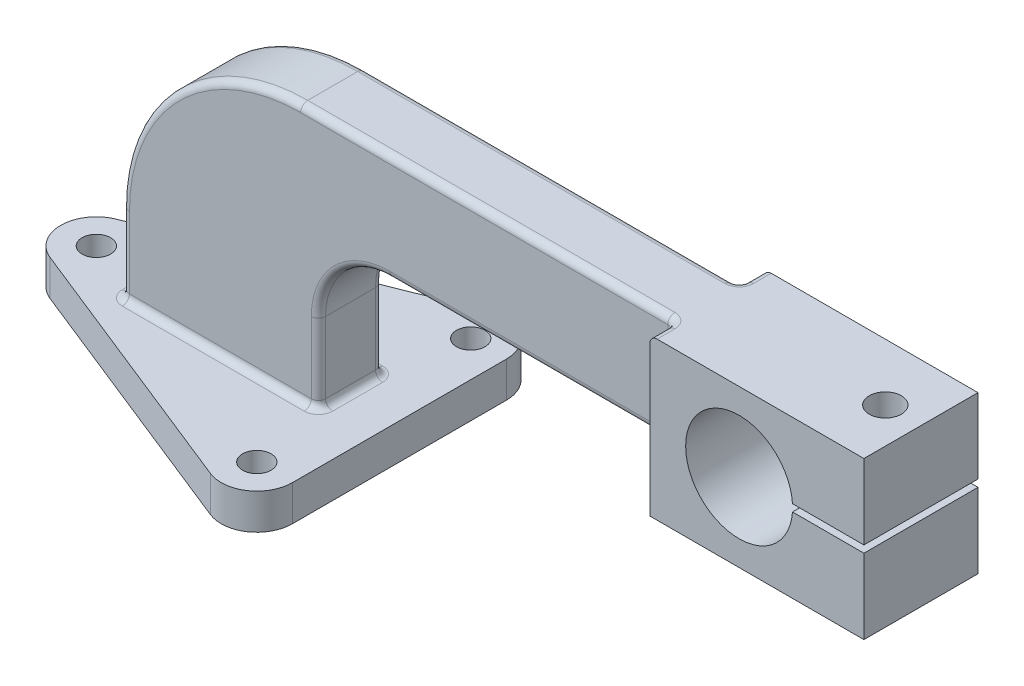
SolidWorks part; units mm, degrees
ref_plane "Front Plane" through (0, 0, 0) normal (0, 0, 1) x (1, 0, 0)
ref_plane "Top Plane" through (0, 0, 0) normal (0, 1, 0) x (1, 0, 0)
ref_plane "Right Plane" through (0, 0, 0) normal (1, 0, 0) x (0, 0, -1)
sketch "Sketch1" plane through (0, 0, 0) normal (0, 1, 0) x (1, 0, 0)
  line L0 (23.2119, 9.2848) -> (98.2119, 39.2848)
  line L1 (111.9258, 30) -> (111.9258, -30)
  line L2 (98.2119, -39.2848) -> (23.2119, -9.2848)
  line L3 (-21.5344, 0) -> (141.3067, 0) construction
  arc A0 (111.9258, -30) -> (98.2119, -39.2848) centre (101.9258, -30) cw
  arc A1 (23.2119, 9.2848) -> (23.2119, -9.2848) centre (26.9258, 0) ccw
  arc A2 (98.2119, 39.2848) -> (111.9258, 30) centre (101.9258, 30) cw
  circle A3 centre (26.9258, 0) radius 4
  circle A4 centre (101.9258, 30) radius 4
  circle A5 centre (101.9258, -30) radius 4
  point P13 (0, 0)
  dimension "D1" = 10
  dimension "D2" = 8
  dimension "D3" = 75
  dimension "D4" = 60
extrude "Boss-Extrude1" add sketch "Sketch1" along normal blind 10
sketch "Sketch2" plane through (0, 0, 0) normal (0, 0, 1) x (1, 0, 0)
  line L0 (43.2119, 10) -> (43.2119, 32)
  line L1 (23.2119, 10) -> (98.2119, 10) construction
  line L2 (98.2119, 10) -> (98.2119, 32)
  line L3 (93.2119, 82) -> (198.2119, 82)
  line L4 (223.2119, 60) -> (258.2119, 60) construction
  line L5 (198.2119, 82) -> (258.2119, 82)
  line L6 (258.2119, 82) -> (258.2119, 38)
  line L7 (258.2119, 38) -> (198.2119, 38)
  line L8 (198.2119, 38) -> (198.2119, 52)
  line L9 (198.2119, 52) -> (118.2119, 52)
  line L10 (98.2119, 10) -> (43.2119, 10)
  line L11 (198.2119, 82) -> (198.2119, 52)
  line L12 (198.2119, 52) -> (198.4483, 50.3894)
  line L14 (234.0634, 61) -> (282.3604, 61)
  line L15 (234.0634, 61) -> (234.0634, 59)
  line L16 (234.0634, 59) -> (282.3604, 59)
  line L17 (282.3604, 61) -> (282.3604, 59)
  line L18 (234.0634, 61) -> (282.3604, 59) construction
  line L19 (234.0634, 59) -> (282.3604, 61) construction
  arc A0 (43.2119, 32) -> (93.2119, 82) centre (93.2119, 32) cw
  arc A1 (98.2119, 32) -> (118.2119, 52) centre (118.2119, 32) cw
  circle A2 centre (223.2119, 60) radius 15
  dimension "D3" = 50
  dimension "D4" = 20
  dimension "D10" = 35
  dimension "D11" = 30
  dimension "D1" = 20
  dimension "D2" = 55
  dimension "D5" = 30
  dimension "D6" = 60
  dimension "D7" = 44
  dimension "D8" = 22
  dimension "D9" = 22
  dimension "D12" = 200
  dimension "D13" = 2
extrude "Boss-Extrude2" add sketch "Sketch2" along normal mid plane 18 contours L2 A1 L9 L11 L3 A0 L0 L10 region at (108.1975, 53.652, 0)
extrude "Boss-Extrude3" add sketch "Sketch2<4>" along normal mid plane 32 contours A2 L6 L5 L11 L8 L7 region at (228.2119, 81.256, 0)
sketch "Sketch2<4>" plane through (0, 0, 0) normal (0, 0, 1) x (1, 0, 0) same geometry as "Sketch2"
sketch "Sketch3" plane through (0, 82, 0) normal (0, 1, 0) x (1, 0, 0)
  line L0 (198.2119, 16) -> (258.2119, 16) construction
  line L1 (258.2119, -16) -> (258.2119, 16) construction
  circle A0 centre (248.2119, 0) radius 4.5
  dimension "D1" = 9
  dimension "D2" = 16
  dimension "D3" = 10
extrude "Cut-Extrude1" cut sketch "Sketch3" against normal through all
fillet "Fillet5" radius 2 21 edges at (198.2119, 82, 12.5) (198.2119, 52, 0) (198.2119, 82, -12.5) (43.2119, 10, 0) (98.2119, 10, 0) (70.7119, 10, 9) (43.2119, 21, 9) (57.8566, 67.3553, 9) (145.7119, 82, 9) (198.2119, 67, 9) (158.2119, 52, 9) (104.0698, 46.1421, 9) (98.2119, 21, 9) (104.0698, 46.1421, -9) (158.2119, 52, -9) (198.2119, 67, -9) (145.7119, 82, -9) (57.8566, 67.3553, -9) (43.2119, 21, -9) (70.7119, 10, -9) (98.2119, 21, -9)
